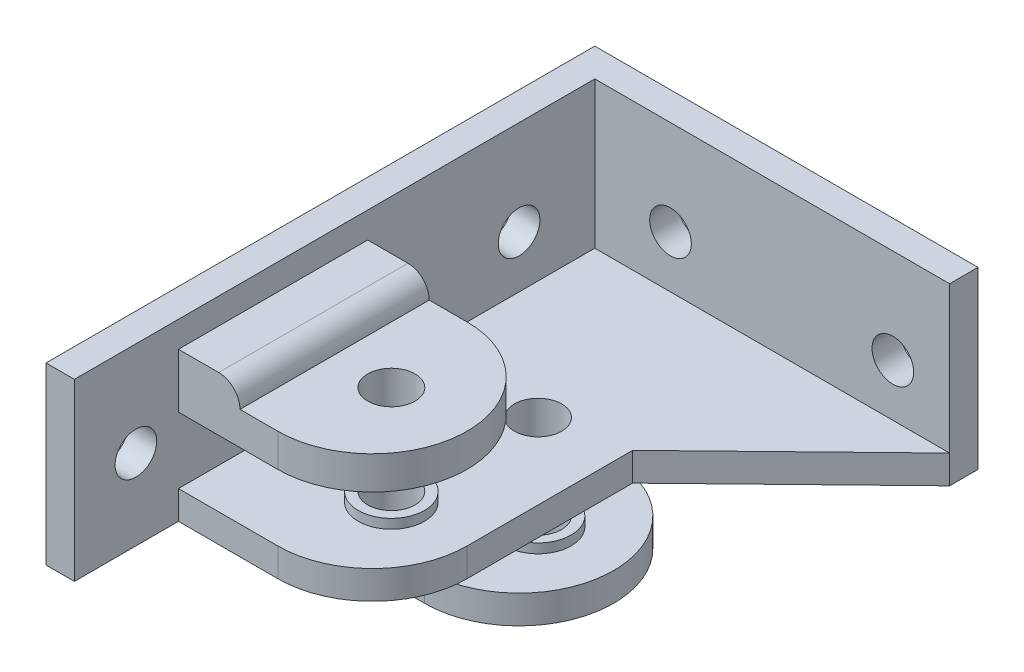
SolidWorks part; units mm, degrees
material "ABS"
ref_plane "Front Plane" through (0, 0, 0) normal (0, 0, 1) x (1, 0, 0)
ref_plane "Top Plane" through (0, 0, 0) normal (0, 1, 0) x (1, 0, 0)
ref_plane "Right Plane" through (0, 0, 0) normal (1, 0, 0) x (0, 0, -1)
sketch "Sketch1" plane through (0, 0, 0) normal (0, 1, 0) x (1, 0, 0)
  line L0 (40.5, 0) -> (0, 0)
  line L1 (0, 0) -> (0, -58)
  line L2 (0, -58) -> (3, -58)
  line L3 (3, -58) -> (3, -3)
  line L4 (3, -3) -> (40.5, -3)
  line L5 (40.5, -3) -> (40.5, 0)
  dimension "D1" = 3
  dimension "D2" = 40.5
  dimension "D3" = 58
extrude "Boss-Extrude1" add sketch "Sketch1" along normal blind 18.5
sketch "Sketch2" plane through (0, 0, 0) normal (0, -1, 0) x (1, 0, 0)
  line L0 (40.5, 3) -> (23.5, 19.5)
  line L1 (23.5, 19.5) -> (23.5, 37)
  line L2 (13.5, 47) -> (3, 47)
  line L3 (3, 3) -> (3, 58) construction
  line L4 (3, 47) -> (3, 3)
  line L5 (3, 3) -> (40.5, 3)
  line L7 (3, 58) -> (0, 58) construction
  line L8 (40.5, 0) -> (0, 0) construction
  arc A0 (13.5, 47) -> (23.5, 37) centre (13.5, 37) cw
  dimension "D3" = 19.5
  dimension "D1" = 10
  dimension "D2" = 17
  dimension "D4" = 11
extrude "Boss-Extrude2" add sketch "Sketch2" against normal blind 3
sketch "Sketch3" plane through (0, 3, 0) normal (0, 1, 0) x (1, 0, 0)
  line L0 (3, -47) -> (13.5, -47)
  line L1 (3, -3) -> (3, -47) construction
  line L2 (13.5, -27) -> (3, -27)
  line L3 (3, -27) -> (3, -47)
  arc A0 (13.5, -27) -> (13.5, -47) centre (13.5, -37) cw
  dimension "D1" = 20
  dimension "D3" = 20.5
extrude "Boss-Extrude3" add sketch "Sketch3" along normal blind 3.5 from offset 7
sketch "Sketch4" plane through (0, 0, 47) normal (0, 0, 1) x (1, 0, 0)
  line L0 (3, 13.5) -> (3, 15.75)
  line L1 (3, 15.75) -> (9.5, 15.75)
  line L2 (9.5, 15.75) -> (9.5, 13.5)
  line L4 (9.5, 13.5) -> (3, 13.5)
  dimension "D1" = 6.5
  dimension "D2" = 2.25
extrude "Boss-Extrude4" add sketch "Sketch4" against normal up to surface (20 mm away) up to face at (8.25, 11.75, 27)
fillet "Fillet1" radius 2.25 1 edges at (9.5, 15.75, 37)
sketch "Sketch5" plane through (0, 0, 0) normal (0, -1, 0) x (1, 0, 0)
  line L0 (0, 31.5) -> (0, 11.5)
  line L1 (0, 58) -> (0, 0) construction
  line L2 (0, 11.5) -> (9, 11.5)
  line L3 (9, 11.5) -> (9, 13.5)
  line L4 (9, 13.5) -> (3, 13.5)
  line L5 (3, 13.5) -> (3, 31.5)
  line L6 (3, 31.5) -> (0, 31.5)
  line L7 (3, 58) -> (0, 58) construction
  line L8 (3, 47) -> (3, 58) construction
  dimension "D1" = 20
  dimension "D2" = 26.5
  dimension "D3" = 2
  dimension "D4" = 9
extrude "Boss-Extrude5" add sketch "Sketch5" along normal blind 7
sketch "Sketch6" plane through (0, -7, 0) normal (0, -1, 0) x (1, 0, 0)
  line L0 (0, 11.5) -> (0, 31.5)
  line L1 (0, 31.5) -> (13.5, 31.5)
  line L2 (13.5, 11.5) -> (0, 11.5)
  arc A0 (13.5, 31.5) -> (13.5, 11.5) centre (13.5, 21.5) cw
  dimension "D1" = 23.5
extrude "Boss-Extrude6" add sketch "Sketch6" along normal blind 3
sketch "Sketch7" plane through (0, 13.5, 0) normal (0, 1, 0) x (1, 0, 0)
  line L2 (0, 0) -> (0, -58) construction
  line L3 (7.25, -47) -> (3, -47) construction
  circle A0 centre (15.5, -21.5) radius 2.5
  circle A1 centre (15.5, -37) radius 2.5
  dimension "D1" = 5
  dimension "D2" = 15.5
  dimension "D3" = 15.5
  dimension "D4" = 10
extrude "Cut-Extrude1" cut sketch "Sketch7" against normal through all
sketch "Sketch8" plane through (0, 0, 0) normal (-1, 0, 0) x (0, 0, 1)
  line L2 (0, 18.5) -> (58, 18.5) construction
  line L3 (0, 18.5) -> (0, 0) construction
  circle A0 centre (11, 8.5) radius 2.2
  circle A1 centre (51.5, 8.5) radius 2.2
  dimension "D1" = 4.4
  dimension "D2" = 40.5
  dimension "D3" = 10
  dimension "D4" = 11
extrude "Cut-Extrude2" cut sketch "Sketch8" against normal through all
sketch "Sketch9" plane through (0, 0, 0) normal (0, 0, -1) x (-1, 0, 0)
  line L2 (-40.5, 18.5) -> (0, 18.5) construction
  line L3 (-40.5, 18.5) -> (-40.5, 0) construction
  circle A0 centre (-34.5, 8.5) radius 2.2
  circle A1 centre (-11, 8.5) radius 2.2
  dimension "D1" = 10
  dimension "D2" = 23.5
  dimension "D3" = 4.4
  dimension "D4" = 6
extrude "Cut-Extrude3" cut sketch "Sketch9" against normal up to next
sketch "Sketch10" plane through (0, -7, 0) normal (0, 1, 0) x (1, 0, 0)
  circle A0 centre (15.5, -21.5) radius 2.5
  circle A1 centre (15.5, -21.5) radius 3.5
  dimension "D1" = 5
  dimension "D2" = 7
extrude "Boss-Extrude7" add sketch "Sketch10" along normal up to next
sketch "Sketch11" plane through (0, 3, 0) normal (0, 1, 0) x (1, 0, 0)
  circle A0 centre (15.5, -37) radius 3.5
  circle A2 centre (15.5, -37) radius 2.5
  dimension "D1" = 7
  dimension "D2" = 5
extrude "Boss-Extrude8" add sketch "Sketch11" along normal up to next
sketch "Sketch12" plane through (0, 0, 47) normal (0, 0, 1) x (1, 0, 0)
  line L0 (19, -7) -> (19, 0) construction
  line L1 (19, -1) -> (12, -1)
  line L2 (19, -1) -> (19, -6)
  line L3 (19, -6) -> (12, -6)
  line L4 (12, -1) -> (12, -6)
  line L5 (12, 0) -> (12, -7) construction
  line L6 (19, 3) -> (19, 10) construction
  line L7 (19, 9) -> (12, 9)
  line L8 (19, 9) -> (19, 4)
  line L9 (19, 4) -> (12, 4)
  line L10 (12, 9) -> (12, 4)
  line L11 (12, 10) -> (12, 3) construction
  line L12 (12, 6.5) -> (19, 6.5) construction
  line L13 (12, -3.5) -> (19, -3.5) construction
  dimension "D1" = 5
  dimension "D2" = 5
extrude "Cut-Extrude4" cut sketch "Sketch12" against normal up to surface (44 mm away) up to face at (8.8, 8.5, 3)
chamfer "Chamfer1" distance 1.5 angle 45 1 edges at (9, -3.5, 13.5)
